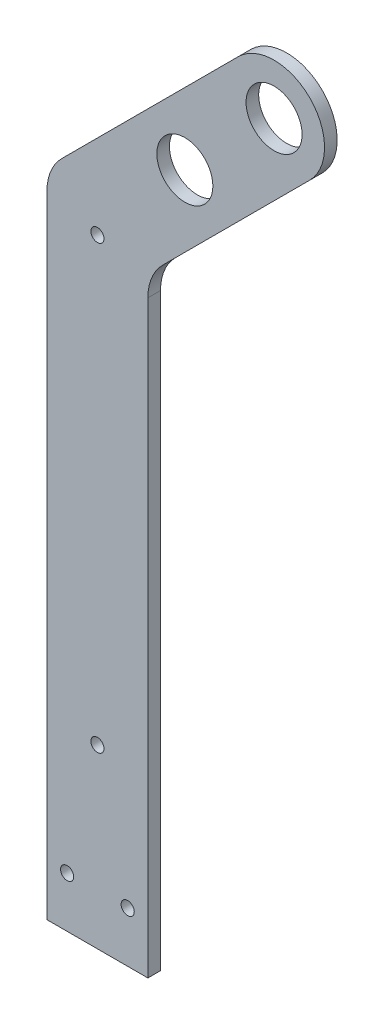
SolidWorks part; units mm, degrees
material "6061 合金"
ref_plane "前视基准面" through (0, 0, 0) normal (0, 0, 1) x (1, 0, 0)
ref_plane "上视基准面" through (0, 0, 0) normal (0, 1, 0) x (1, 0, 0)
ref_plane "右视基准面" through (0, 0, 0) normal (1, 0, 0) x (0, 0, -1)
other "Configuration Table"
sketch "草图1" plane through (0, 0, 0) normal (0, 0, 1) x (1, 0, 0)
  circle A0 centre (0, 0) radius 20
  circle A1 centre (0, 0) radius 11.1
  dimension "D1" = 40
  dimension "D2" = 22.2
extrude "凸台-拉伸1" add sketch "草图1" along normal blind 60 contours A1 | A0 region at (0, 0, 0)
ref_plane "基准面1" through (0, 0, 30) normal (0, 0, 1) x (1, 0, 0)
sketch "草图2" plane through (0, 0, 30) normal (0, 0, 1) x (1, 0, 0)
  line L0 (0, 0) -> (-70, -70) construction
  line L1 (-70, -70) -> (-70, -320) construction
  line L2 (0, -57.3148) -> (0, 49.9409) construction
  line L3 (-56.8582, 0) -> (46.4003, 0) construction
  line L4 (-14.1421, 14.1421) -> (-90, -61.7157)
  line L5 (14.1421, -14.1421) -> (-50, -78.2843)
  line L6 (-90, -61.7157) -> (-90, -320)
  line L7 (-50, -78.2843) -> (-50, -320)
  line L8 (-90, -320) -> (-50, -320)
  circle A2 centre (0, 0) radius 20 construction
  arc A3 (-14.1421, 14.1421) -> (14.1421, -14.1421) centre (0, 0) ccw
  dimension "D1" = 45
  dimension "D2" = 250
  dimension "D3" = 70
  dimension "D4" = 40
  dimension "D5" = 40
extrude "凸台-拉伸2" add sketch "草图2" along normal mid plane 60 contours L7 L8 L6 L4 A3 L5
sketch "草图4" plane through (0, 0, 60) normal (0, 0, 1) x (1, 0, 0)
  line L0 (-90, -61.7157) -> (-90, -320) construction
  line L1 (-90, -290) -> (-50, -290)
  line L2 (-90, -290) -> (-90, -350)
  line L4 (-50, -290) -> (-50, -350)
  line L5 (-50, -78.2843) -> (-50, -320) construction
  line L6 (-90, -320) -> (-50, -320) construction
  arc A0 (-90, -350) -> (-50, -350) centre (-70, -350) ccw
  circle A1 centre (-70, -350) radius 11
  dimension "D3" = 22
  dimension "D1" = 30
  dimension "D2" = 30
extrude "凸台-拉伸3" add sketch "草图4" along normal blind 5
mirror "镜向1" about plane through (0, 0, 30) normal (0, 0, 1) of "凸台-拉伸3"
sketch "草图5" plane through (0, 0, 0) normal (0, 1, 0) x (1, 0, 0)
  line L0 (0, 0) -> (0, -78.0582) construction
ref_plane "基准面2" through (-70, 0, 0) normal (-1, 0, 0) x (0, 0, 1)
sketch "草图7" plane through (-70, 0, 0) normal (-1, 0, 0) x (0, 0, 1)
  line L0 (-34.1239, -350) -> (109.535, -350) construction
sketch "草图8" plane through (0, 0, 60) normal (0, 0, 1) x (1, 0, 0)
  line L0 (0, 0) -> (-70, -70) construction
  circle A0 centre (-35.3553, -35.3553) radius 11.1
  dimension "D1" = 22.2
  dimension "D2" = 50
extrude "切除-拉伸1" cut sketch "草图8" against normal blind 100
fillet "圆角4" radius 20 2 edges at (-90, -61.7157, 30) (-50, -78.2843, 30)
fillet "圆角1" [suppressed] radius 50
fillet "圆角2" [suppressed] radius 3
sketch "草图9" plane through (0, 0, 65) normal (0, 0, 1) x (1, 0, 0)
  circle A0 centre (-70, -350) radius 13
  dimension "D1" = 26
extrude "切除-拉伸2" [suppressed] cut sketch "草图9" against normal blind 0.75
sketch "草图10" plane through (0, 0, -5) normal (0, 0, -1) x (-1, 0, 0)
  circle A0 centre (70, -350) radius 13
  dimension "D1" = 26
extrude "切除-拉伸3" [suppressed] cut sketch "草图10" against normal blind 0.75 contours A0
sketch "草图11" plane through (-90, 0, 0) normal (-1, 0, 0) x (0, 0, 1)
  circle A0 centre (48.5, -118.9949) radius 2.75
  circle A1 centre (48.5, -183.9949) radius 2.75
  circle A2 centre (48.5, -248.9949) radius 2.75
  circle A3 centre (11.5, -248.9949) radius 2.75
  circle A4 centre (11.5, -183.9949) radius 2.75
  circle A5 centre (11.5, -118.9949) radius 2.75
  dimension "D1" = 5.5
extrude "切除-拉伸4" [suppressed] cut sketch "草图11" against normal through all contours A1 | A2 | A0 | A3 | A4 | A5
sketch "草图12" [suppressed] plane through (-90, 0, 0) normal (-1, 0, 0) x (0, 0, 1)
  line L0 (30, -62.0134) -> (30, -339.6946) construction
  line L1 (10, -128.9949) -> (50, -128.9949)
  line L2 (10, -128.9949) -> (10, -173.9949)
  line L3 (10, -173.9949) -> (50, -173.9949)
  line L4 (50, -128.9949) -> (50, -173.9949)
  line L5 (10, -193.9949) -> (50, -193.9949)
  line L6 (10, -193.9949) -> (10, -238.9949)
  line L7 (10, -238.9949) -> (50, -238.9949)
  line L8 (50, -193.9949) -> (50, -238.9949)
  line L9 (10, -258.9949) -> (50, -258.9949)
  line L10 (10, -258.9949) -> (10, -290)
  line L11 (10, -290) -> (50, -290)
  line L12 (50, -258.9949) -> (50, -290)
  line L13 (19.5, -173.9949) -> (40.5, -173.9949)
  line L14 (19.5, -173.9949) -> (19.5, -193.9949)
  line L15 (19.5, -193.9949) -> (40.5, -193.9949)
  line L16 (40.5, -173.9949) -> (40.5, -193.9949)
  line L17 (19.5, -238.9949) -> (40.5, -238.9949)
  line L18 (19.5, -238.9949) -> (19.5, -258.9949)
  line L19 (19.5, -258.9949) -> (40.5, -258.9949)
  line L20 (40.5, -238.9949) -> (40.5, -258.9949)
  line L21 (60, -82.4264) -> (60, -290) construction
  line L22 (0, -290) -> (0, -82.4264) construction
  line L23 (57, -320) -> (3, -320) construction
  circle A0 centre (48.5, -118.9949) radius 2.75 construction
  circle A1 centre (48.5, -183.9949) radius 2.75 construction
  circle A2 centre (48.5, -248.9949) radius 2.75 construction
  dimension "D1" = 10
  dimension "D2" = 10
  dimension "D3" = 10
  dimension "D4" = 8
  dimension "D5" = 10
  dimension "D6" = 10
  dimension "D7" = 10
  dimension "D8" = 30
extrude "减重" [suppressed] cut sketch "草图12" against normal through all contours L0 L1 L2 L3 | L15 L0 L17 L7 L8 L5 | L0 L5 L6 L7 | L19 L0 L11 L12 L9 | L0 L9 L10 L11 | L1 L0 L13 L3 L4
fillet "圆角3" [suppressed] radius 3
sketch "草图13" plane through (0, 0, 60) normal (0, 0, 1) x (1, 0, 0)
  circle A0 centre (0, 0) radius 13
  circle A1 centre (-35.3553, -35.3553) radius 13
  dimension "D1" = 26
  dimension "D2" = 26
extrude "切除-拉伸6" [suppressed] cut sketch "草图13" against normal blind 1.75
sketch "草图14" plane through (0, 0, 0) normal (0, 0, -1) x (-1, 0, 0)
  circle A0 centre (0, 0) radius 13
  circle A1 centre (35.3553, -35.3553) radius 13
  dimension "D1" = 26
  dimension "D2" = 26
extrude "切除-拉伸7" [suppressed] cut sketch "草图14" against normal blind 1.75
sketch "草图15" [suppressed] plane through (0, 0, 0) normal (0, 0, -1) x (-1, 0, 0)
  line L0 (0, 0) -> (70, -350) construction
  line L1 (56.2719, -67.2005) -> (60.1942, -86.8121) construction
  line L2 (70, -350) -> (204.3541, -323.1292) construction
  circle A0 centre (56.2719, -67.2005) radius 2.75
  circle A1 centre (75.2172, -73.6095) radius 2.75
  circle A2 centre (60.1942, -86.8121) radius 2.75
  dimension "D1" = 5.5
  dimension "D2" = 20
  dimension "D3" = 20
  dimension "D4" = 20
  dimension "D5" = 42
  dimension "D6" = 270
extrude "切除-拉伸8" [suppressed] cut sketch "草图15" against normal through all contours A2 | A0 | A1
ref_plane "小腿主干连杆面" through (0, 0, 0) normal (0.9806, -0.1961, 0) x (0, 0, -1)
ref_plane "小腿主干对称面" through (0, 0, 30) normal (0, 0, -1) x (-1, 0, 0)
sketch "草图16" plane through (0, 0, 60) normal (0, 0, 1) x (1, 0, 0)
  line L0 (0, 0) -> (-70, -350)
  line L1 (-35.3553, -35.3553) -> (0, 0)
sketch "草图17" plane through (0, 0, 60) normal (0, 0, 1) x (1, 0, 0)
  line L0 (0, 0) -> (-70, -350) construction
  line L1 (118.6974, 32.5948) -> (32.9122, -396.3312) construction
  line L2 (92.7764, -97.0102) -> (20.2919, -82.5133)
  line L3 (73.1648, -195.0683) -> (0.6803, -180.5713)
  circle A0 centre (20.2919, -82.5133) radius 46
  circle A1 centre (0.6803, -180.5713) radius 46
  dimension "D3" = 92
  dimension "D4" = 92
  dimension "D1" = 110
  dimension "D2" = 73.92
  dimension "D5" = 180
  dimension "D6" = 280
sketch "草图18" plane through (0, 0, 60) normal (0, 0, 1) x (1, 0, 0)
  line L1 (14.1421, -14.1421) -> (-44.1421, -72.4264) construction
  line L3 (14.1421, -14.1421) -> (-44.1421, -72.4264)
  line L4 (15.4873, -12.6548) -> (52.8188, -49.9864)
  line L5 (-50, -128.5133) -> (20.2919, -128.5133)
  line L10 (-90, -290) -> (-50, -290)
  line L11 (-50, -290) -> (-50, -86.5685)
  line L12 (-44.1421, -72.4264) -> (14.1421, -14.1421)
  line L13 (-14.1421, 14.1421) -> (-84.1421, -55.8579)
  line L14 (-90, -70) -> (-90, -290)
  line L16 (-50, -128.5133) -> (-50, -86.5685)
  line L17 (-44.1421, -72.4264) -> (14.1421, -14.1421)
  circle A0 centre (20.2919, -82.5133) radius 46 construction
  arc A1 (14.1421, -14.1421) -> (-14.1421, 14.1421) centre (0, 0) ccw construction
  arc A2 (14.1421, -14.1421) -> (-14.1421, 14.1421) centre (0, 0) ccw
  arc A3 (14.1421, -14.1421) -> (15.4873, -12.6548) centre (0, 0) ccw
  arc A4 (20.2919, -128.5133) -> (52.8188, -49.9864) centre (20.2919, -82.5133) ccw
  circle A5 centre (20.2919, -82.5133) radius 35
  arc A9 (-84.1421, -55.8579) -> (-90, -70) centre (-70, -70) ccw
  arc A10 (-84.1421, -55.8579) -> (-90, -70) centre (-70, -70) ccw
  arc A11 (-44.1421, -72.4264) -> (-50, -86.5685) centre (-30, -86.5685) ccw
  arc A12 (-44.1421, -72.4264) -> (-50, -86.5685) centre (-30, -86.5685) ccw
  line M14 (-50, -290) -> (-50, -86.5685)
  line M15 (-44.1421, -72.4264) -> (14.1421, -14.1421)
  arc M16 (14.1421, -14.1421) -> (-14.1421, 14.1421) centre (0, 0) ccw
  arc M22 (-50, -86.5685) -> (-44.1421, -72.4264) centre (-30, -86.5685) cw
  dimension "D2" = 70
  dimension "D1" = 0
extrude "凸台-拉伸4" add sketch "草图18" against normal blind 5 from offset 25 contours L5 A4 L4 A5 M16 M15 M22 M14 region at (16.0508, -14.5165, 60) offset against normal yes
sketch "草图19" plane through (0, 0, 0) normal (0, 0, -1) x (-1, 0, 0)
  line L0 (50, -86.5685) -> (50, -290) construction
  line L1 (50, -134.5713) -> (50, -226.5713)
  line L2 (-0.6803, -134.5713) -> (50, -134.5713)
  line L3 (-0.6803, -226.5713) -> (50, -226.5713)
  circle A0 centre (-0.6803, -180.5713) radius 46 construction
  arc A1 (-0.6803, -134.5713) -> (-0.6803, -226.5713) centre (-0.6803, -180.5713) ccw
  circle A2 centre (-0.6803, -180.5713) radius 35
  dimension "D1" = 70
extrude "凸台-拉伸5" add sketch "草图19" against normal blind 5 from offset 25 offset against normal yes
fillet "圆角5" radius 10 2 edges at (-50, -226.5713, 27.5) (-50, -128.5133, 32.5)
sketch "草图21" plane through (0, 0, 65) normal (0, 0, 1) x (1, 0, 0)
  line L0 (-70, -350) -> (-70, -6.9331) construction
  circle A0 centre (-70, -75) radius 2.6
  circle A1 centre (-70, -250) radius 2.6
  circle A2 centre (-58, -300) radius 2.6
  circle A3 centre (-82, -300) radius 2.6
  dimension "D1" = 5.2
  dimension "D2" = 12
  dimension "D3" = 50
  dimension "D4" = 100
  dimension "D5" = 175
extrude "切除-拉伸9" cut sketch "草图21" against normal through all both and the other way through all
sketch "草图22" plane through (-90, 0, 0) normal (-1, 0, 0) x (0, 0, 1)
  line L0 (-5, -350) -> (-5, -370) construction
  line L5 (-5, -389.7985) -> (20, -389.7985)
  line L6 (-5, -389.7985) -> (-5, 64.9179)
  line L7 (-5, 64.9179) -> (20, 64.9179)
  line L8 (20, -389.7985) -> (20, 64.9179)
  line L10 (65, -370) -> (25, -370)
  line L11 (65, -370) -> (65, 61.088)
  line L12 (65, 61.088) -> (25, 61.088)
  line L13 (25, -370) -> (25, 61.088)
  dimension "D1" = 40
  dimension "D2" = 5
extrude "切除-拉伸10" cut sketch "草图22" against normal through all both contours L8 L7 L6 L5 | L13 L12 L11 L10
